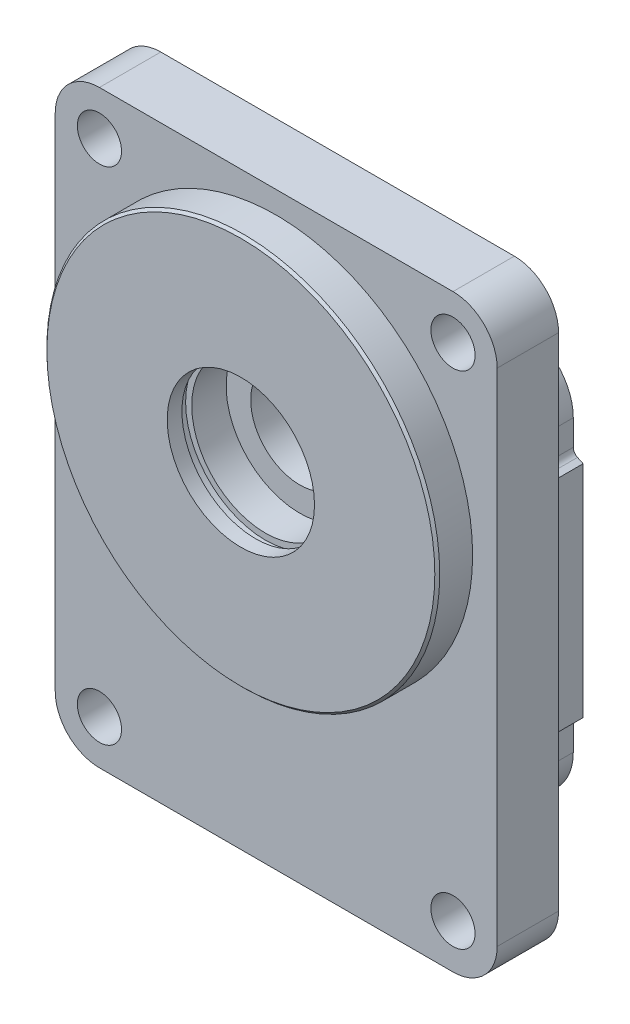
SolidWorks part; units mm, degrees
ref_plane "Front Plane" through (0, 0, 0) normal (0, 0, 1) x (1, 0, 0)
ref_plane "Top Plane" through (0, 0, 0) normal (0, 1, 0) x (1, 0, 0)
ref_plane "Right Plane" through (0, 0, 0) normal (1, 0, 0) x (0, 0, -1)
sketch "Sketch1" plane through (0, 0, 0) normal (0, 0, 1) x (1, 0, 0)
  line L1 (-36, 60) -> (36, 60)
  line L2 (-45, 51) -> (-45, -51)
  line L3 (-36, -60) -> (36, -60)
  line L4 (45, 51) -> (45, -51)
  line L5 (-45, 60) -> (45, -60) construction
  line L6 (-45, -60) -> (45, 60) construction
  arc A0 (-45, -51) -> (-36, -60) centre (-36, -51) ccw
  arc A1 (36, -60) -> (45, -51) centre (36, -51) ccw
  arc A2 (36, 60) -> (45, 51) centre (36, 51) cw
  arc A3 (-36, 60) -> (-45, 51) centre (-36, 51) ccw
  circle A4 centre (-36, 51) radius 4.5
  circle A5 centre (36, 51) radius 4.5
  circle A6 centre (36, -51) radius 4.5
  circle A7 centre (-36, -51) radius 4.5
  point P0 (0, 0)
  dimension "D3" = 9
  dimension "D4" = 9
  dimension "D1" = 90
  dimension "D2" = 120
extrude "Boss-Extrude1" add sketch "Sketch1" along normal blind 12.5
sketch "Sketch2" plane through (0, 0, 12.5) normal (0, 0, 1) x (1, 0, 0)
  line L0 (0, 0) -> (0, 50.1147) construction
  line L1 (0, 0) -> (35.3903, 0) construction
  circle A0 centre (0, 15.5) radius 40
  dimension "D2" = 80
  dimension "D1" = 15.5
extrude "Boss-Extrude2" add sketch "Sketch2" along normal blind 7.2
sketch "Sketch3" plane through (0, 0, 19.7) normal (0, 0, 1) x (1, 0, 0)
  circle A0 centre (0, 15.5) radius 10
  dimension "D1" = 20
extrude "Cut-Extrude1" cut sketch "Sketch3" against normal through all
sketch "Sketch5" plane through (0, 0, 0) normal (0, 0, -1) x (-1, 0, 0)
  line L0 (0, 0) -> (0, 50.3035) construction
  line L1 (0, 0) -> (-43.3881, 0) construction
  line L2 (-40, 29.5) -> (-40, 24.2874)
  line L3 (-40.8586, 22.9315) -> (-42, 22.3916)
  line L4 (-42, 22.3916) -> (-42, -22.3916)
  line L5 (42, 22.3916) -> (42, -22.3916)
  line L6 (40.8586, 22.9315) -> (42, 22.3916)
  line L7 (40, 29.5) -> (40, 24.2874)
  line L8 (40, -29.5) -> (40, -24.2874)
  line L9 (40.8586, -22.9315) -> (42, -22.3916)
  line L10 (-40.8586, -22.9315) -> (-42, -22.3916)
  line L11 (-40, -29.5) -> (-40, -24.2874)
  arc A0 (28.2748, 41.2375) -> (-28.2748, 41.2375) centre (0, 0) ccw
  circle A1 centre (-29, 29.5) radius 5.1 construction
  arc A3 (-30.4453, 40.4046) -> (-40, 29.5) centre (-29, 29.5) ccw
  arc A4 (-40, 24.2874) -> (-40.8586, 22.9315) centre (-41.5, 24.2874) cw
  arc A5 (-28.2748, 41.2375) -> (-30.4453, 40.4046) centre (-31.1023, 45.3613) cw
  circle A6 centre (29, 29.5) radius 5.1 construction
  arc A7 (40, 24.2874) -> (40.8586, 22.9315) centre (41.5, 24.2874) ccw
  arc A8 (30.4453, 40.4046) -> (40, 29.5) centre (29, 29.5) cw
  arc A9 (28.2748, 41.2375) -> (30.4453, 40.4046) centre (31.1023, 45.3613) ccw
  arc A10 (-29.3283, 40.4951) -> (28.2748, 41.2375) centre (0, 0) cw
  arc A11 (28.2748, -41.2375) -> (-28.2748, -41.2375) centre (0, 0) cw
  circle A12 centre (29, -29.5) radius 5.1 construction
  circle A13 centre (-29, -29.5) radius 5.1 construction
  arc A14 (28.2748, -41.2375) -> (30.4453, -40.4046) centre (31.1023, -45.3613) cw
  arc A15 (30.4453, -40.4046) -> (40, -29.5) centre (29, -29.5) ccw
  arc A16 (40, -24.2874) -> (40.8586, -22.9315) centre (41.5, -24.2874) cw
  arc A17 (-28.2748, -41.2375) -> (-30.4453, -40.4046) centre (-31.1023, -45.3613) ccw
  arc A18 (-40, -24.2874) -> (-40.8586, -22.9315) centre (-41.5, -24.2874) ccw
  arc A19 (-30.4453, -40.4046) -> (-40, -29.5) centre (-29, -29.5) cw
  point P10 (-29.3283, -40.4951)
  point P15 (0, 0)
  point P18 (-29.3283, 40.4951)
  point P49 (42, 0)
  point P50 (-42, 0)
  circle M7 centre (0, 15.5) radius 10
  dimension "D3" = 50
  dimension "D4" = 10.2
  dimension "D1" = 11
  dimension "D5" = 1.5
  dimension "D6" = 5
  dimension "D2" = 29
  dimension "D7" = 42
  dimension "D8" = 29.5
extrude "Boss-Extrude7" add sketch "Sketch5" along normal blind 8 contours A19 A17 A11 A14 A15 L8 A16 L9 L5 L6 A7 L7 A8 A9 A0 A5 A3 L2 A4 L3 L4 L10 A18 L11 M7 region at (0, -0.6952, 0)
fillet "Fillet1" radius 1 24 edges at (-41.4293, 22.6615, 0) (-40.2327, 23.485, 0) (-40, 26.8937, 0) (-37.2734, 36.7492, 0) (-29.311, 40.6932, 0) (41.4293, 22.6615, 0) (40.2327, 23.485, 0) (40, 26.8937, 0) (37.2734, 36.7492, 0) (29.311, 40.6932, 0) (41.4293, -22.6615, 0) (40.2327, -23.485, 0) (40, -26.8937, 0) (37.2734, -36.7492, 0) (29.311, -40.6932, 0) (0, -50, 0) (-29.311, -40.6932, 0) (-41.4293, -22.6615, 0) (-40.2327, -23.485, 0) (-40, -26.8937, 0) (0, 50, 0) (42, 0, 0) (-37.2734, -36.7492, 0) (-42, 0, 0)
hole_wizard "M10 Tapped Hole1" positions "Sketch6" profile "Sketch7" tap size "M10" standard "ISO"
sketch "Sketch6" plane through (0, 0, -8) normal (0, 0, -1) x (-1, 0, 0)
  point P0 (-26.3489, 29.5)
  point P2 (31.6511, 29.5)
  point P4 (31.6511, -29.5)
  point P6 (-26.3489, -29.5)
  point P14 (-26.3489, -34.357)
  point P15 (0, 0)
  point P16 (0, 0)
  point P17 (0, 0)
  point P18 (0, 0)
  dimension "D1" = 58
  dimension "D2" = 26.3489
  dimension "D3" = 59
  dimension "D4" = 29.5
sketch "Sketch7" plane through (26.3489, 29.5, -8) normal (1, 0, 0) x (0, 1, 0)
  line L0 (0, 0) -> (0, 19.5537)
  line L1 (0, 19.5537) -> (4.25, 17)
  line L2 (4.25, 17) -> (4.25, 0)
  line L5 (4.25, 0) -> (0, 0)
  line L10 (0, 19.5537) -> (-4.25, 17) construction
  line L11 (0, -6.35) -> (0, 107.95) construction
  dimension "Tap Drill Dia." = 8.5
  dimension "Tap Drill Depth" = 17
  dimension "Drill Angle" = 118
cosmetic thread "Hole Thread1" parameters "D1"=20, "D2"=10
cosmetic thread "Hole Thread2" parameters "D1"=20, "D2"=10
cosmetic thread "Hole Thread3" parameters "D1"=20, "D2"=10
cosmetic thread "Hole Thread4" parameters "D1"=20, "D2"=10
sketch "Sketch8" plane through (0, 0, 0) normal (0, 0, -1) x (-1, 0, 0)
  circle A0 centre (-36, -51) radius 8
  circle A1 centre (36, -51) radius 8
  circle A2 centre (36, 51) radius 8
  circle A3 centre (-36, 51) radius 8
  dimension "D1" = 16
extrude "Cut-Extrude2" cut sketch "Sketch8" against normal blind 0.5
sketch "Sketch9" plane through (0, 0, 19.7) normal (0, 0, 1) x (1, 0, 0)
  circle A0 centre (0, 15.5) radius 15
  dimension "D1" = 30
extrude "Cut-Extrude3" cut sketch "Sketch9" against normal blind 12
sketch "Sketch10" plane through (0, 0, 0) normal (1, 0, 0) x (0, 0, -1)
  line L0 (-7.7, 30.5) -> (-19.7, 30.5) construction
  line L1 (-16.7, 31.75) -> (-14.7, 31.75)
  line L2 (-16.7, 31.75) -> (-16.7, 29.25)
  line L3 (-16.7, 29.25) -> (-14.7, 29.25)
  line L4 (-14.7, 31.75) -> (-14.7, 29.25)
  line L5 (-16.7, 31.75) -> (-14.7, 29.25) construction
  line L6 (-16.7, 29.25) -> (-14.7, 31.75) construction
  line L7 (-19.7, 55.5) -> (-19.7, -24.5) construction
  line L8 (-7.7, 15.5) -> (-22.778, 15.5) construction
  line L9 (-7.7, 30.5) -> (-7.7, 0.5) construction
  point P0 (-15.7, 30.5)
  dimension "D1" = 2
  dimension "D2" = 2.5
  dimension "D3" = 3
revolve "Cut-Revolve2" cut sketch "Sketch10" angle 360 about L8
chamfer "Chamfer1" distance 0.5 angle 45 1 edges at (40, 15.5, 19.7)
hole_wizard "Ø4.0 (4) Diameter Hole1" positions "Sketch11" profile "Sketch12" hole size "Ø4.0" standard "ISO"
sketch "Sketch11" plane through (0, 0, -8) normal (0, 0, -1) x (-1, 0, 0)
  point P0 (0, 45)
  point P2 (0, -45)
  dimension "D1" = 45
  dimension "D2" = 45
sketch "Sketch12" plane through (0, 45, -8) normal (1, 0, 0) x (0, 1, 0)
  line L0 (0, 0) -> (0, 4.2017)
  line L1 (0, 4.2017) -> (2, 3)
  line L2 (2, 3) -> (2, 0)
  line L5 (2, 0) -> (0, 0)
  line L10 (0, 4.2017) -> (-2, 3) construction
  line L11 (0, -6.35) -> (0, 107.95) construction
  dimension "Hole Dia." = 4
  dimension "Hole Depth" = 3
  dimension "Drill Angle" = 118
